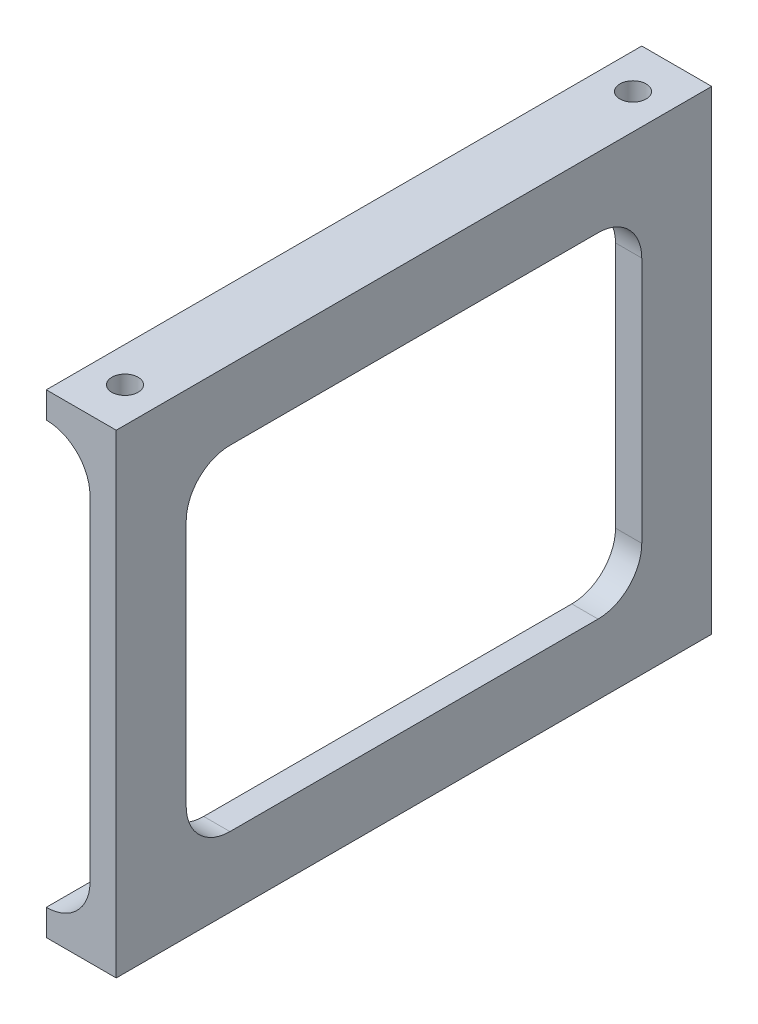
SolidWorks part; units mm, degrees
ref_plane "Front Plane" through (0, 0, 0) normal (0, 0, 1) x (1, 0, 0)
ref_plane "Top Plane" through (0, 0, 0) normal (0, 1, 0) x (1, 0, 0)
ref_plane "Right Plane" through (0, 0, 0) normal (1, 0, 0) x (0, 0, -1)
sketch "Sketch1" plane through (0, -6.8481, 0) normal (0, 1, 0) x (1, 0, 0)
  line L0 (88.75, 20.1693) -> (98.75, 20.1693) construction
  line L1 (98.75, 88.2635) -> (95.75, 88.2635)
  line L2 (98.75, 88.2635) -> (98.75, 20.1693)
  line L3 (98.75, 20.1693) -> (95.75, 20.1693)
  line L4 (95.75, 88.2635) -> (95.75, 20.1693)
  dimension "D1" = 3
extrude "Main extrude" add sketch "Sketch1" along normal up to surface (54.25 mm away)
sketch "Sketch2" plane through (0, 47.4019, 0) normal (0, 1, 0) x (1, 0, 0)
  line L1 (98.75, 88.2635) -> (90.75, 88.2635)
  line L2 (98.75, 88.2635) -> (98.75, 20.1693)
  line L3 (98.75, 20.1693) -> (90.75, 20.1693)
  line L4 (90.75, 88.2635) -> (90.75, 20.1693)
  point P5 (98.75, 20.1693)
  dimension "D1" = 8
extrude "Top screwhole extension" add sketch "Sketch2" against normal blind 3
sketch "Sketch3" plane through (0, -6.8481, 0) normal (0, -1, 0) x (1, 0, 0)
  line L1 (98.75, -20.1693) -> (90.75, -20.1693)
  line L2 (98.75, -20.1693) -> (98.75, -88.2635)
  line L3 (98.75, -88.2635) -> (90.75, -88.2635)
  line L4 (90.75, -20.1693) -> (90.75, -88.2635)
  point P5 (98.75, -88.2635)
  dimension "D1" = 8
extrude "Bottom screwhole extension" add sketch "Sketch3" against normal blind 3
fillet "Screwhole extension fillets 5mm" radius 5 2 edges at (95.75, 44.4019, -54.2164) (95.75, -3.8481, -54.2164)
sketch "Sketch4" plane through (0, -6.8481, 0) normal (0, -1, 0) x (1, 0, 0)
  line L0 (98.75, -20.1693) -> (98.75, -88.2635) construction
  line L1 (98.75, -88.2635) -> (90.75, -88.2635) construction
  line L2 (90.75, -20.1693) -> (98.75, -20.1693) construction
  circle A0 centre (94.75, -25.1693) radius 1.5
  circle A1 centre (94.75, -83.2635) radius 1.5
  point P4 (0, 0)
  point P5 (0, 0)
  point P8 (94.75, -83.0455)
  dimension "D1" = 3
  dimension "D2" = 4
  dimension "D3" = 5
  dimension "D4" = 5
extrude "Bottom screwholes" cut sketch "Sketch4" against normal blind 8
sketch "Sketch5" plane through (0, 47.4019, 0) normal (0, 1, 0) x (1, 0, 0)
  circle A0 centre (94.75, 25.1693) radius 1.5 construction
  circle A1 centre (94.75, 25.1693) radius 1.5
  circle A2 centre (94.75, 83.2635) radius 1.5 construction
  circle A3 centre (94.75, 83.2635) radius 1.5
extrude "Top screwholes" cut sketch "Sketch5" against normal blind 8
sketch "Sketch6" plane through (98.75, 0, 0) normal (1, 0, 0) x (0, 0, -1)
  line L8 (28.1693, 39.4019) -> (28.1693, 1.1519)
  line L9 (28.1693, 1.1519) -> (80.2635, 1.1519)
  line L10 (80.2635, 1.1519) -> (80.2635, 39.4019)
  line L11 (80.2635, 39.4019) -> (28.1693, 39.4019)
  line L12 (28.1693, 34.4019) -> (28.1693, 6.1519)
  line L13 (33.1693, 1.1519) -> (75.2635, 1.1519)
  line L14 (80.2635, 6.1519) -> (80.2635, 34.4019)
  line L15 (75.2635, 39.4019) -> (33.1693, 39.4019)
  arc A0 (28.1693, 6.1519) -> (33.1693, 1.1519) centre (33.1693, 6.1519) ccw
  arc A1 (75.2635, 1.1519) -> (80.2635, 6.1519) centre (75.2635, 6.1519) ccw
  arc A2 (80.2635, 34.4019) -> (75.2635, 39.4019) centre (75.2635, 34.4019) ccw
  arc A3 (28.1693, 34.4019) -> (33.1693, 39.4019) centre (33.1693, 34.4019) cw
  dimension "D2" = 5
  dimension "D1" = 8
extrude "Weight reduction" cut sketch "Sketch6" against normal through all both and the other way through all
